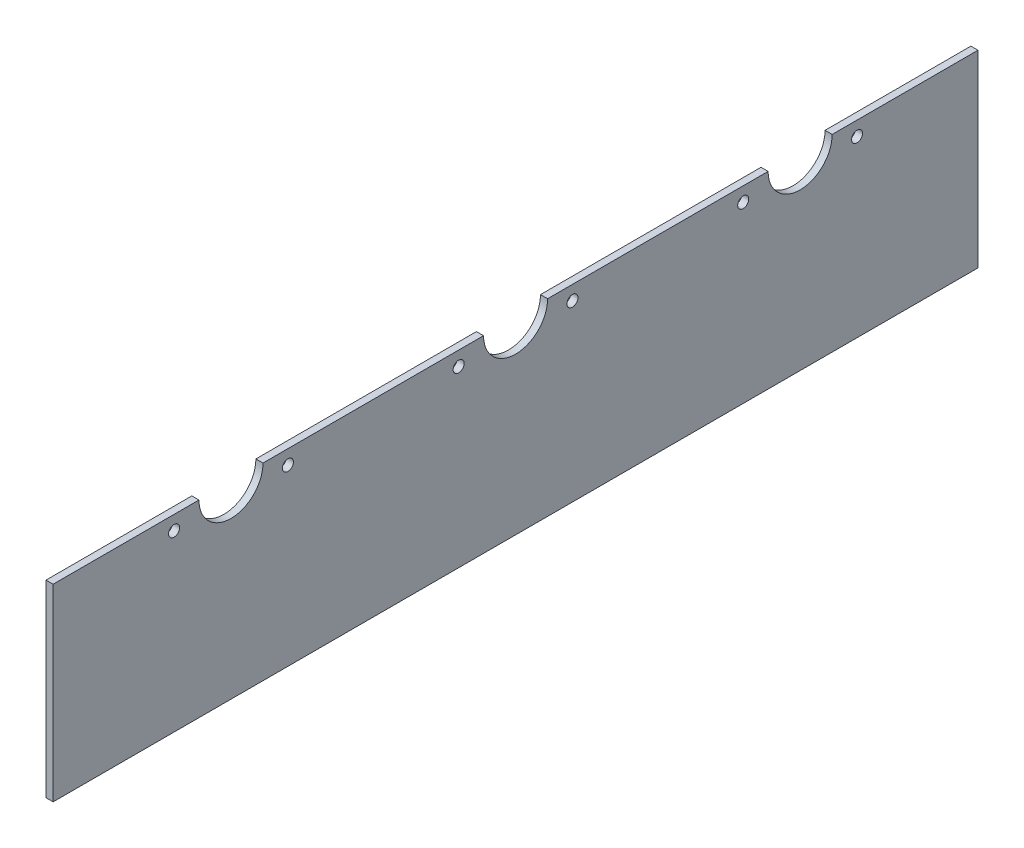
SolidWorks part; units mm, degrees
ref_plane "Front Plane" through (0, 0, 0) normal (0, 0, 1) x (1, 0, 0)
ref_plane "Top Plane" through (0, 0, 0) normal (0, 1, 0) x (1, 0, 0)
ref_plane "Right Plane" through (0, 0, 0) normal (1, 0, 0) x (0, 0, -1)
sketch "Sketch1" plane through (0, 0, 0) normal (1, 0, 0) x (0, 0, -1)
  line L0 (206.375, 0) -> (-206.375, 0)
  line L1 (-206.375, 0) -> (-206.375, 84.1375)
  line L2 (-206.375, 84.1375) -> (-141.2875, 84.1375)
  line L3 (-112.7125, 84.1375) -> (-14.2875, 84.1375)
  line L4 (14.2875, 84.1375) -> (112.7125, 84.1375)
  line L5 (141.2875, 84.1375) -> (206.375, 84.1375)
  line L6 (206.375, 84.1375) -> (206.375, 0)
  line L7 (-206.375, 25.4) -> (206.375, 25.4) construction
  arc A6 (-141.2875, 84.1375) -> (-112.7125, 84.1375) centre (-127, 84.1375) ccw
  arc A7 (-14.2875, 84.1375) -> (14.2875, 84.1375) centre (0, 84.1375) ccw
  arc A8 (112.7125, 84.1375) -> (141.2875, 84.1375) centre (127, 84.1375) ccw
  point P4 (0, 0)
  dimension "D1" = 25.4
  dimension "D5" = 28.575
  dimension "D6" = 44.45
  dimension "D2" = 412.75
  dimension "D4" = 127
extrude "Boss-Extrude1" add sketch "Sketch1" along normal blind 3.175
hole_wizard "#10 (0.1935) Diameter Hole1" positions "Sketch2" profile "Sketch3" hole size "#10" standard "ANSI Inch" end condition through all
sketch "Sketch2" plane through (3.175, 0, 0) normal (1, 0, 0) x (0, 0, -1)
  line L0 (-152.4, 77.7875) -> (-101.6, 77.7875) construction
  line L2 (-25.4, 77.7875) -> (25.4, 77.7875) construction
  line L4 (101.6, 77.7875) -> (152.4, 77.7875) construction
  line L6 (-141.2875, 84.1375) -> (-206.375, 84.1375) construction
  line L7 (-127, 77.7875) -> (-127, 84.1375) construction
  line L9 (0, 84.1375) -> (0, 77.7875) construction
  line L11 (127, 84.1375) -> (127, 77.7875) construction
  point P0 (-152.4, 77.7875)
  point P2 (-101.6, 77.7875)
  point P4 (-25.4, 77.7875)
  point P6 (25.4, 77.7875)
  point P8 (101.6, 77.7875)
  point P10 (152.4, 77.7875)
  dimension "D1" = 50.8
  dimension "D2" = 6.35
sketch "Sketch3" plane through (3.175, 77.7875, 152.4) normal (0, 1, 0) x (0, 0, -1)
  line L0 (0, 0) -> (0, 3.175)
  line L1 (0, 3.175) -> (2.4574, 3.175)
  line L2 (2.4574, 3.175) -> (2.4574, 0)
  line L5 (2.4574, 0) -> (0, 0)
  line L11 (0, -6.35) -> (0, 107.95) construction
  dimension "Thru Hole Dia." = 4.9149
  dimension "Thru Hole Depth" = 3.175
